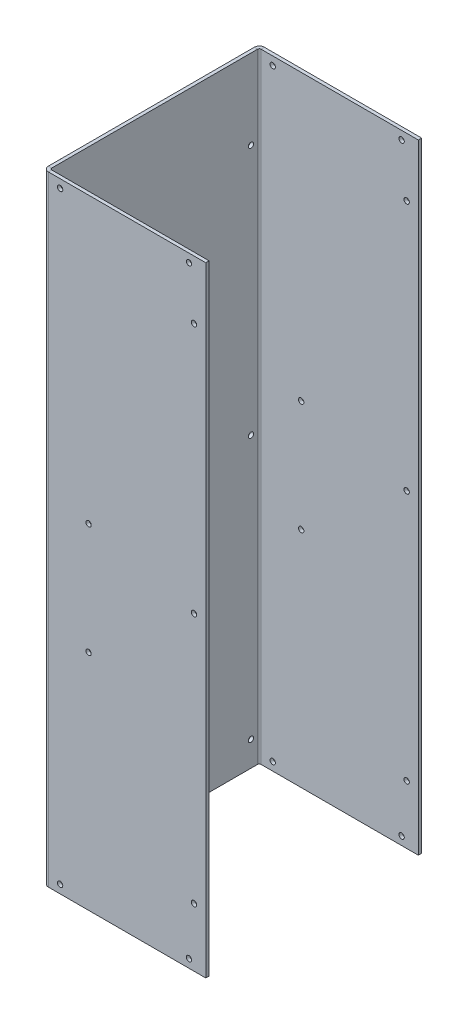
SolidWorks part; units mm, degrees
note: The reader was unsure of these and kept them because the rebuilt part matched: flange length of "Edge-Flange2".
ref_plane "Front Plane" through (0, 0, 0) normal (1, 0, 0) x (0, 1, 0)
ref_plane "Top Plane" through (0, 0, 0) normal (0, 0, 1) x (0, 1, 0)
ref_plane "Right Plane" through (0, 0, 0) normal (0, 1, 0) x (-1, 0, 0)
sketch "Sketch1" plane through (0, 0, 0) normal (1, 0, 0) x (0, 1, 0)
  line L6 (185, -64.5) -> (-185, -64.5)
  line L12 (185, -64.5) -> (185, 64.5)
  line L13 (185, 64.5) -> (-185, 64.5)
  line L14 (-185, -64.5) -> (-185, 64.5)
  line L15 (185, -64.5) -> (-185, 64.5) construction
  line L16 (185, 64.5) -> (-185, -64.5) construction
  line L17 (-180, 64.5) -> (142.3, 64.5) construction
  line L18 (-180, 64.5) -> (-180, -64.5) construction
  line L19 (-180, -64.5) -> (142.3, -64.5) construction
  line L20 (142.3, 64.5) -> (142.3, -64.5) construction
  circle A0 centre (-170, 57.5) radius 1.6
  circle A1 centre (137.3, 57.5) radius 1.6
  circle A2 centre (-170, -57.5) radius 1.6
  circle A3 centre (137.3, -57.5) radius 1.6
  circle A4 centre (34.3, 57.5) radius 1.6
  circle A5 centre (-12.7, -57.5) radius 1.6
  point P0 (0, 0)
  point P18 (0, 0)
  point P19 (0, 0)
  point P24 (0, 0)
  dimension "D3" = 3.2
  dimension "D10" = 150
  dimension "D1" = 129
  dimension "D2" = 370
  dimension "D4" = 7
  dimension "D5" = 322.3
  dimension "D6" = 7
  dimension "D7" = 5
  dimension "D8" = 10
  dimension "D9" = 5
  dimension "D11" = 103
base flange "Base-Flange2" sketch "Sketch1" thickness 2 reverse thickness direction no parameters "D1"=0.9652
edge flange "Edge-Flange2" sketch "Sketch21" flange profiles "Sketch21", "Sketch22" flange angle 90 flange length 97 flange position material inside bend radius 0.9652 thickness 2 relief rectangular parameters "D1"=0.7366, "D6"=10, "D8"=1
sketch "Sketch21" plane through (0, 0, -64.5) normal (0, 0, -1) x (0, 1, 0)
  line L0 (-185, 0) -> (185, 0) construction
  line L1 (185, 0) -> (-185, 0)
  line L2 (185, 0) -> (185, 95)
  line L3 (185, 95) -> (-185, 95)
  line L4 (-185, 95) -> (-185, 0)
sketch "Sketch22" plane through (0, 0, 64.5) normal (0, 0, 1) x (0, -1, 0)
  line L0 (-185, 0) -> (185, 0) construction
  line L1 (-185, 0) -> (185, 0)
  line L2 (-185, 0) -> (-185, 95)
  line L3 (-185, 95) -> (185, 95)
  line L4 (185, 95) -> (185, 0)
bend "EdgeBend2" bend radius 0.9652 bend angle 90 parameters "D5"=1
bend "EdgeBend3" bend radius 0.9652 bend angle 90 parameters "D5"=2
sketch "Sketch23" plane through (0, 0, -64.5) normal (0, 0, -1) x (1, 0, 0)
  line L0 (0, -185) -> (0, 185) construction
  line L1 (95, -185) -> (95, 185) construction
  line L2 (95, 185) -> (0.9652, 185) construction
  line L3 (0.9652, -185) -> (95, -185) construction
  line L4 (-2, -185) -> (-2, 185) construction
  circle A0 centre (88, 150) radius 1.6
  circle A1 centre (88, 0) radius 1.6
  circle A2 centre (88, -150) radius 1.6
  circle A3 centre (8, 180) radius 1.6
  circle A4 centre (85, 180) radius 1.6
  circle A5 centre (8, -180) radius 1.6
  circle A6 centre (85, -180) radius 1.6
  circle A7 centre (25, -15) radius 1.6
  circle A8 centre (25, 51.5) radius 1.6
  point P10 (0, 0)
  point P29 (0, 0)
  dimension "D1" = 3.2
  dimension "D5" = 5
  dimension "D9" = 66.5
  dimension "D10" = 3.2
  dimension "D2" = 150
  dimension "D3" = 150
  dimension "D4" = 7
  dimension "D6" = 5
  dimension "D7" = 10
  dimension "D8" = 10
  dimension "D11" = 27
  dimension "D12" = 170
extrude "Cut-Extrude2" cut sketch "Sketch23" against normal through all normal cut yes
sketch "Bend-Lines3" [suppressed] plane through (0, 0, 0) normal (0, 1, 0) x (-1, 0, 0)
sketch "Bounding-Box3" [suppressed] plane through (0, 0, 0) normal (0, 1, 0) x (-1, 0, 0)
sheet metal parameters "Sheet-Metal5" thickness 2 parameters "D1"=0.7366
flat pattern "Flat-Pattern5" [suppressed]
sketch "Bend-Lines4" plane through (0, 0, 0) normal (0, 1, 0) x (-1, 0, 0)
sketch "Bounding-Box4" [suppressed] plane through (0, 0, 0) normal (0, 1, 0) x (-1, 0, 0)
sheet metal parameters "Sheet-Metal6" thickness 2 parameters "D1"=0.7366
flat pattern "Flat-Pattern5" [suppressed]
sketch "Bend-Lines4" plane through (0, 0, 0) normal (0, 1, 0) x (-1, 0, 0)
sketch "Bounding-Box4" [suppressed] plane through (0, 0, 0) normal (0, 1, 0) x (-1, 0, 0)
bend of the flat pattern "Flatten-<EdgeBend2>1"
bend of the flat pattern "Flatten-<EdgeBend3>1"
sheet metal parameters "Sheet-Metal7" thickness 2 parameters "D1"=0.7366
flat pattern "Flat-Pattern5"
sketch "Bend-Lines4" plane through (0, 0, 0) normal (1, 0, 0) x (0, 1, 0)
  line L0 (185, 63.0783) -> (-185, 63.0783) construction
  line L1 (-185, -63.0783) -> (185, -63.0783) construction
  line L2 (185, 63.0783) -> (-185, 63.0783) construction
  line L3 (-185, -63.0783) -> (185, -63.0783) construction
sketch3d "Bounding-Box4" [suppressed]
  line L0 (185, -158.6565, 0) -> (-185, -158.6565, 0) construction
  line L1 (185, 158.6565, 0) -> (-185, 158.6565, 0) construction
  line L2 (185, -158.6565, 0) -> (185, 158.6565, 0) construction
  line L3 (-185, -158.6565, 0) -> (-185, 158.6565, 0) construction
bend of the flat pattern "Flatten-<EdgeBend2>1"
bend of the flat pattern "Flatten-<EdgeBend3>1"
